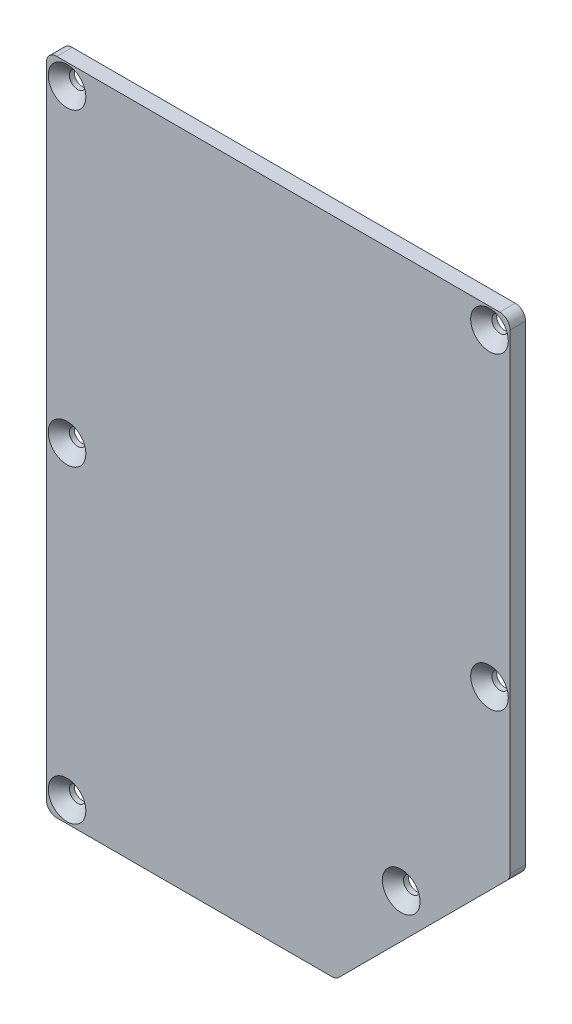
SolidWorks part; units mm, degrees
ref_plane "Front Plane" through (0, 0, 0) normal (0, 0, 1) x (1, 0, 0)
ref_plane "Top Plane" through (0, 0, 0) normal (0, 1, 0) x (1, 0, 0)
ref_plane "Right Plane" through (0, 0, 0) normal (1, 0, 0) x (0, 0, -1)
sketch "Sketch1" plane through (0, 0, 0) normal (0, 0, 1) x (1, 0, 0)
  line L5 (-45, 66) -> (-45, -58)
  line L6 (-43, -60) -> (10.3848, -60)
  line L7 (11.799, -59.4142) -> (44.4142, -26.799)
  line L8 (45, -25.3848) -> (45, 66)
  line L9 (43, 68) -> (-43, 68)
  line L10 (-45, 66) -> (-45, -58)
  line L11 (-43, -60) -> (10.3848, -60)
  line L12 (11.799, -59.4142) -> (44.4142, -26.799)
  line L13 (45, -25.3848) -> (45, 66)
  line L14 (43, 68) -> (-43, 68)
  arc A5 (-45, -58) -> (-43, -60) centre (-43, -58) ccw
  arc A6 (10.3848, -60) -> (11.799, -59.4142) centre (10.3848, -58) ccw
  arc A7 (44.4142, -26.799) -> (45, -25.3848) centre (43, -25.3848) ccw
  arc A8 (45, 66) -> (43, 68) centre (43, 66) ccw
  arc A9 (-43, 68) -> (-45, 66) centre (-43, 66) ccw
  arc A10 (-45, -58) -> (-43, -60) centre (-43, -58) ccw
  arc A11 (10.3848, -60) -> (11.799, -59.4142) centre (10.3848, -58) ccw
  arc A12 (44.4142, -26.799) -> (45, -25.3848) centre (43, -25.3848) ccw
  arc A13 (45, 66) -> (43, 68) centre (43, 66) ccw
  arc A14 (-43, 68) -> (-45, 66) centre (-43, 66) ccw
  dimension "D1" = 0
extrude "Boss-Extrude1" add sketch "Sketch1" along normal blind 3
sketch "Sketch5" plane through (0, 0, 3) normal (0, 0, 1) x (1, 0, 0)
  point P0 (-41, 64)
  point P1 (41, 64)
  point P3 (41, 4)
  point P5 (23.864, -38.864)
  point P7 (-41, -56)
  point P9 (-41, 4)
  point P11 (-41, 64)
hole_wizard "CSK for M3 Countersunk Flat Head Screw1" positions "3DSketch3" profile "Sketch6" countersink size "M3" standard "ISO"
sketch3d "3DSketch3"
  point P0 (-41, -56, 3)
  point P3 (23.864, -38.864, 3)
  point P6 (41, 4, 3)
  point P9 (-41, 4, 3)
  point P12 (-41, 64, 3)
  point P15 (41, 64, 3)
sketch "Sketch6" plane through (-41, -56, 3) normal (1, 0, 0) x (0, -1, 0)
  line L0 (0, 0) -> (0, 5.9614)
  line L1 (0, 5.9614) -> (1.6, 5)
  line L2 (1.6, 5) -> (1.6, 2.05)
  line L3 (1.6, 2.05) -> (3.65, 0)
  line L5 (3.65, 0) -> (0, 0)
  line L6 (-1.6, 2.05) -> (-3.65, 0) construction
  line L10 (0, 5.9614) -> (-1.6, 5) construction
  line L11 (0, -6.35) -> (0, 107.95) construction
  dimension "Hole Dia." = 3.2
  dimension "Hole Depth" = 5
  dimension "Near C'Sink Dia." = 7.3
  dimension "Near C'Sink Angle" = 90
  dimension "Drill Angle" = 118
